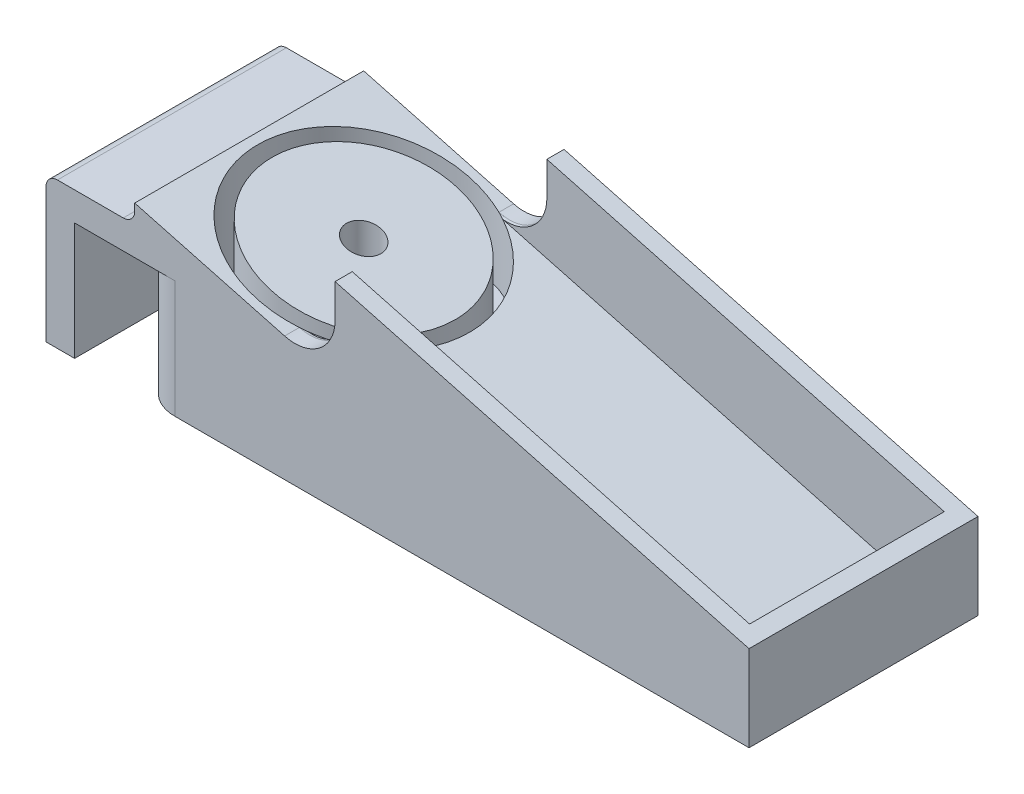
SolidWorks part; units mm, degrees
ref_plane "Piano frontale" through (0, 0, 0) normal (0, 0, 1) x (1, 0, 0)
ref_plane "Piano superiore" through (0, 0, 0) normal (0, 1, 0) x (1, 0, 0)
ref_plane "Piano destro" through (0, 0, 0) normal (1, 0, 0) x (0, 0, -1)
sketch "Schizzo2" plane through (0, 0, 0) normal (0, 0, 1) x (1, 0, 0)
  line L0 (0, 0) -> (0, 10)
  line L1 (0, 10) -> (70, 10)
  line L2 (70, 10) -> (107.3205, 0)
  line L3 (107.3205, 0) -> (0, 0)
  dimension "D1" = 10
  dimension "D2" = 15
  dimension "D3" = 70
extrude "Estrusione-Estrusione2" add sketch "Schizzo2" along normal blind 40
sketch "Schizzo3" plane through (0, 10, 0) normal (0, 1, 0) x (1, 0, 0)
  line L0 (0, 0) -> (70, -40) construction
  line L1 (0, -40) -> (70, 0) construction
  line L2 (0, -40) -> (0, 0) construction
  circle A0 centre (20, -20) radius 16
  circle A1 centre (20, -20) radius 18.5
  point P12 (35, -20)
  dimension "D1" = 32
  dimension "D2" = 2.5
  dimension "D3" = 20
sketch "Schizzo4" plane through (0, 0, 40) normal (0, 0, 1) x (1, 0, 0)
  line L0 (0, 10) -> (0, 28.7564)
  line L1 (0, 28.7564) -> (70, 10)
  line L2 (0, 10) -> (70, 10) construction
  line L3 (107.3205, 0) -> (70, 10) construction
  line L4 (70, 10) -> (0, 10)
extrude "Estrusione-Estrusione3" add sketch "Schizzo4" against normal up to surface (40 mm away) up to face at (44.3301, 5, 0)
extrude "Taglio-Estrusione2" cut sketch "Schizzo3" along normal blind 38
sketch "Schizzo5" plane through (0, 0, 40) normal (0, 0, 1) x (1, 0, 0)
  line L0 (35, 19.3782) -> (35, 34.3782)
  line L1 (107.3205, 0) -> (0, 28.7564) construction
  line L2 (35, 34.3782) -> (107.3205, 15)
  line L3 (107.3205, 15) -> (107.3205, 0)
  line L4 (107.3205, 0) -> (35, 19.3782)
  line L5 (0, 28.7564) -> (0, 0) construction
  dimension "D1" = 35
  dimension "D2" = 15
extrude "Estrusione-Estrusione4" add sketch "Schizzo5" against normal blind 3
ref_plane "Piano1" through (0, 0, 20) normal (0, 0, 1) x (1, 0, 0)
mirror "Specchia1" about plane through (0, 0, 20) normal (0, 0, 1) of "Estrusione-Estrusione4"
sketch "Schizzo6" plane through (107.3205, 0, 0) normal (1, 0, 0) x (0, 0, -1)
  line L1 (-37, 15) -> (-3, 15)
  line L2 (-37, 15) -> (-37, 0)
  line L3 (-37, 0) -> (-3, 0)
  line L4 (-3, 15) -> (-3, 0)
extrude "Estrusione-Estrusione5" add sketch "Schizzo6" along direction (-0.9659, 0.2588, 0) on the side against the normal blind 3
sketch "Schizzo7" plane through (0, 0, 0) normal (0, -1, 0) x (1, 0, 0)
  line L0 (18.908, 20) -> (-18.908, 20) construction
  circle A0 centre (20, 20) radius 3
  dimension "D1" = 6
extrude "Taglio-Estrusione4" cut sketch "Schizzo7" against normal through all
sketch "Schizzo9" plane through (0, 0, 0) normal (0, -1, 0) x (1, 0, 0)
  line L0 (18.908, 20) -> (-18.908, 20) construction
  circle A0 centre (20, 20) radius 4
  circle A1 centre (20, 20) radius 3 construction
  dimension "D1" = 8
extrude "Taglio-Estrusione5" cut sketch "Schizzo9" against normal blind 7 from offset 10 offset against normal yes
sketch "Schizzo11" plane through (0, 0, 0) normal (-1, 0, 0) x (0, 0, 1)
  line L0 (0, 28.7564) -> (0, 0) construction
  line L1 (0, 25.5) -> (40, 25.5)
  line L2 (0, 25.5) -> (0, 20.5)
  line L3 (0, 20.5) -> (40, 20.5)
  line L4 (40, 25.5) -> (40, 20.5)
  line L5 (40, 28.7564) -> (40, 0) construction
  line L6 (40, 0) -> (0, 0) construction
  dimension "D1" = 20.5
  dimension "D2" = 5
extrude "Estrusione-Estrusione6" add sketch "Schizzo11" along normal blind 10.5
sketch "Schizzo12" plane through (0, 25.5, 0) normal (0, 1, 0) x (1, 0, 0)
  line L0 (-10.5, -40) -> (0, -40) construction
  line L1 (-10.5, 0) -> (-15.5, 0)
  line L2 (-10.5, 0) -> (-10.5, -40)
  line L3 (-10.5, -40) -> (-15.5, -40)
  line L4 (-15.5, 0) -> (-15.5, -40)
  dimension "D1" = 5
extrude "Estrusione-Estrusione7" add sketch "Schizzo12" against normal up to surface (25.5 mm away) up to face at (23, 0, 20)
fillet "Raccordo1" radius 2 2 edges at (-15.5, 25.5, 20) (0, 25.5, 20)
fillet "Raccordo2" radius 7 4 edges at (0, 10.25, 0) (0, 10.25, 40) (35, 19.3782, 1.5) (35, 19.3782, 38.5)
